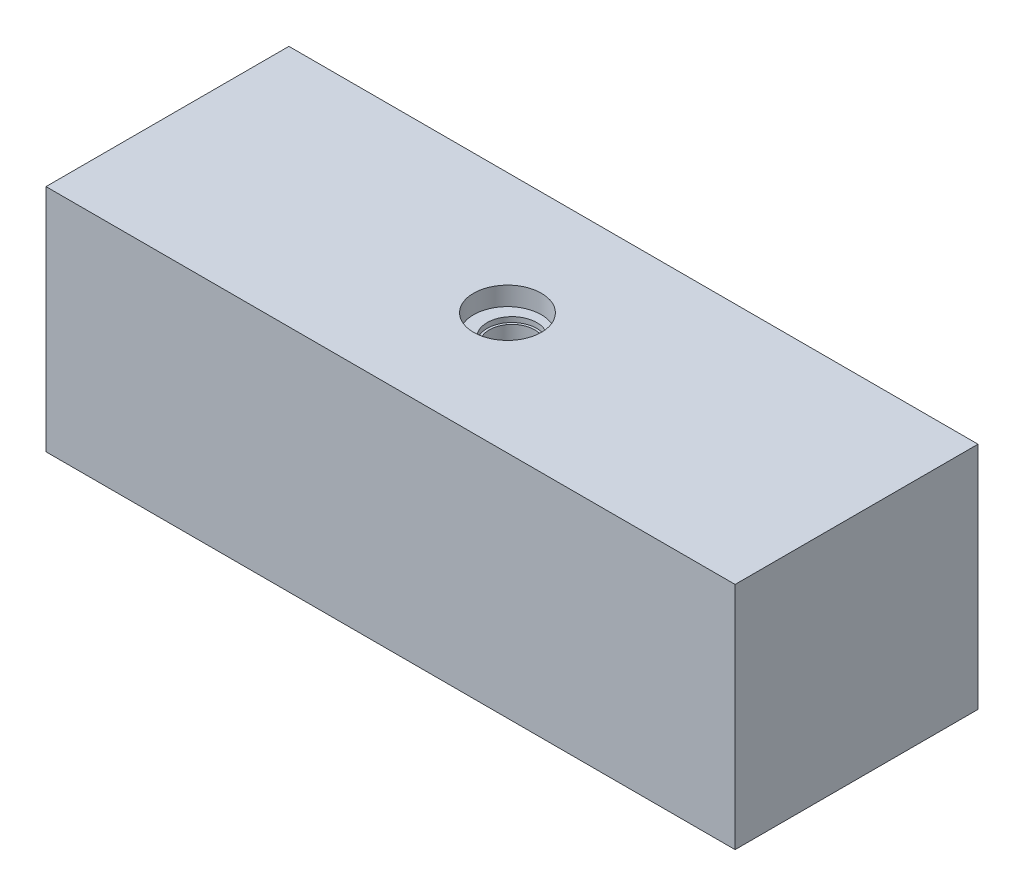
SolidWorks part; units mm, degrees
ref_plane "Front Plane" through (0, 0, 0) normal (0, 0, 1) x (1, 0, 0)
ref_plane "Top Plane" through (0, 0, 0) normal (0, 1, 0) x (1, 0, 0)
ref_plane "Right Plane" through (0, 0, 0) normal (1, 0, 0) x (0, 0, -1)
sketch "Sketch1" plane through (0, 0, 0) normal (0, 1, 0) x (1, 0, 0)
  line L1 (76.2, -26.8605) -> (-76.2, -26.8605)
  line L2 (76.2, -26.8605) -> (76.2, 26.8605)
  line L3 (76.2, 26.8605) -> (-76.2, 26.8605)
  line L4 (-76.2, -26.8605) -> (-76.2, 26.8605)
  line L5 (76.2, -26.8605) -> (-76.2, 26.8605) construction
  line L6 (76.2, 26.8605) -> (-76.2, -26.8605) construction
  point P0 (0, 0)
  dimension "D1" = 53.721
  dimension "D2" = 152.4
extrude "Boss-Extrude1" add sketch "Sketch1" along normal blind 50.8
sketch "Sketch2" plane through (0, 50.8, 0) normal (0, 1, 0) x (1, 0, 0)
  circle A0 centre (0, 0) radius 5
  circle A1 centre (-1, 0) radius 7.5
  circle A3 centre (0, 0) radius 5.5
  dimension "D1" = 10
  dimension "D3" = 11
  dimension "D4" = 15
  dimension "D2" = 1
extrude "Cut-Extrude1" cut sketch "Sketch2" against normal blind 19.4167 contours A0 region at (0, 50.8, 0)
extrude "Cut-Extrude2" cut sketch "Sketch2<4>" against normal blind 5.2542 contours A3 A0 region at (-5.3444, 50.8, 0)
sketch "Sketch2<4>" plane through (0, 50.8, 0) normal (0, 1, 0) x (1, 0, 0) same geometry as "Sketch2"
extrude "Cut-Extrude3" cut sketch "Sketch2<5>" against normal blind 4.1231 contours A1 A3 region at (-8.2879, 50.8, 0)
sketch "Sketch2<5>" plane through (0, 50.8, 0) normal (0, 1, 0) x (1, 0, 0) same geometry as "Sketch2"
